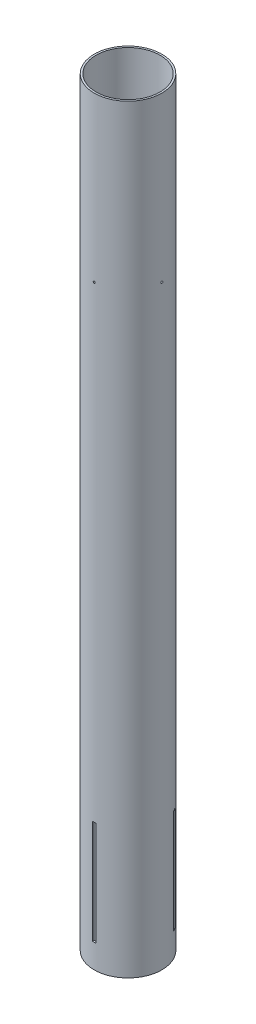
SolidWorks part; units mm, degrees
material "Hexcel AS4C (3000 Filaments)"
ref_plane "Front Plane" through (0, 0, 0) normal (0, 0, 1) x (1, 0, 0)
ref_plane "Top Plane" through (0, 0, 0) normal (0, 1, 0) x (1, 0, 0)
ref_plane "Right Plane" through (0, 0, 0) normal (1, 0, 0) x (0, 0, -1)
sketch "Sketch1" plane through (0, 0, 0) normal (0, 1, 0) x (1, 0, 0)
  circle A0 centre (0, 0) radius 50.8
  dimension "D1" = 101.6
extrude "Body Tube Extrusion" add sketch "Sketch1" along normal blind 1206.5 thin thin type one direction wall 2.921
ref_plane "Plane1" through (0, 0, 53.721) normal (0, 0, 1) x (1, 0, 0)
sketch "Sketch2" plane through (0, 0, 53.721) normal (0, 0, 1) x (1, 0, 0)
  line L0 (0, 1206.5) -> (0, 0) construction
  line L1 (50.8, 1206.5) -> (-50.8, 1206.5) construction
  line L2 (-53.721, 0) -> (53.721, 0) construction
  circle A0 centre (0, 946.15) radius 1.6383
  dimension "D1" = 3.2766
  dimension "D2" = 946.15
extrude "Engine Block Hole" cut sketch "Sketch2" against normal up to next
pattern_circular "CirPattern1" count 4 over 360 about axis through (0, 1206.5, 0) along (0, -1, 0) of "Engine Block Hole"
sketch "Sketch3" plane through (0, 0, 53.721) normal (0, 0, 1) x (1, 0, 0)
  line L0 (0, 0) -> (0, 38.1) construction
  line L1 (-50.8, 0) -> (50.8, 0) construction
  line L2 (0, 1206.5) -> (0, 0) construction
  line L4 (-2.667, 203.2) -> (2.667, 203.2)
  line L5 (-2.667, 203.2) -> (-2.667, 38.1)
  line L6 (-2.667, 38.1) -> (2.667, 38.1)
  line L7 (2.667, 203.2) -> (2.667, 38.1)
  point P10 (0, 38.1)
  dimension "D1" = 165.1
  dimension "D2" = 5.334
  dimension "D3" = 38.1
extrude "Fin Tab Slots" cut sketch "Sketch3" against normal blind 2.54
pattern_circular "CirPattern2" count 3 over 360 about axis through (0, 1206.5, 0) along (0, -1, 0) of "Fin Tab Slots" reverse direction yes
